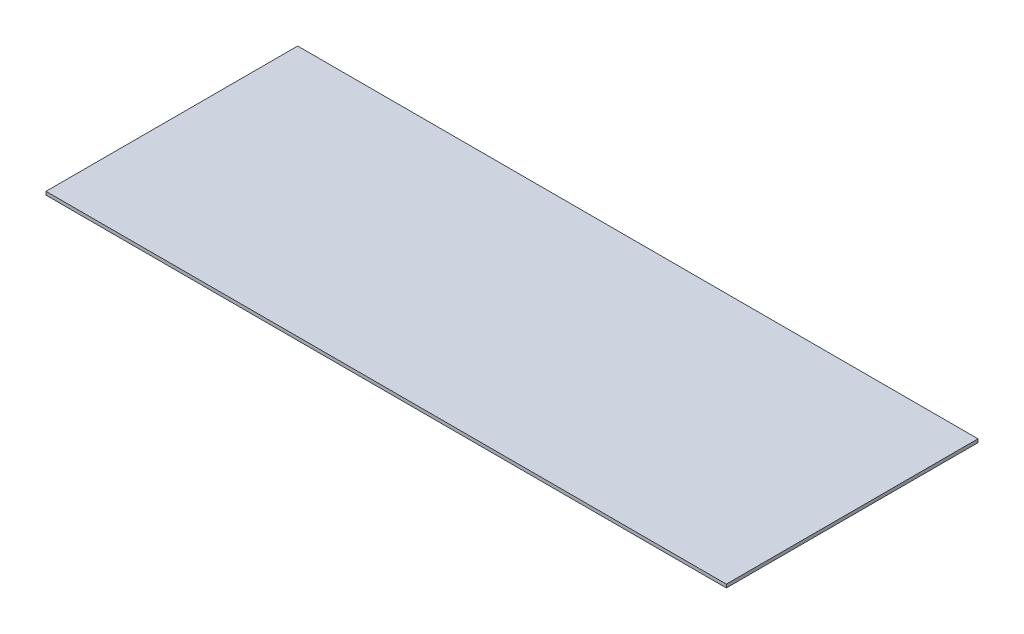
SolidWorks part; units mm, degrees
material "Glas"
ref_plane "Ebene vorne" through (0, 0, 0) normal (0, 0, 1) x (1, 0, 0)
ref_plane "Ebene oben" through (0, 0, 0) normal (0, 1, 0) x (1, 0, 0)
ref_plane "Ebene rechts" through (0, 0, 0) normal (1, 0, 0) x (0, 0, -1)
sketch "Skizze1" plane through (0, 0, 0) normal (0, 0, 1) x (1, 0, 0)
  line L0 (405.5, 0) -> (-405.5, 0)
  line L1 (405.5, 4) -> (-405.5, 4)
  line L2 (-405.5, 4) -> (-405.5, 0)
  line L3 (405.5, 0) -> (405.5, 4)
  point P4 (0, 0)
  point P8 (0, 4)
  dimension "D1" = 4
  dimension "D2" = 811
extrude "Aufsatz-Linear austragen1" add sketch "Skizze1" along normal blind 300
equation "\"wall_thickness\"= 4mm"
equation "\"wall_height\"= 300"
equation "\"D1@Skizze1\"=\"wall_thickness\""
equation "\"D1@Aufsatz-Linear austragen1\"=\"wall_height\""
equation "\"edge_length\"= 800mm"
equation "\"coldplate_circumference\"= 4*\"edge_length\""
equation "\"L-profile_width\"= 20mm"
equation "\"L-profile_thickness\"= 1.5mm"
equation "\"extrusion_width\"= 40mm"
equation "\"D2@Skizze1\"=\"edge_length\" + \"wall_thickness\"*2 + \"L-profile_thickness\"*2"
